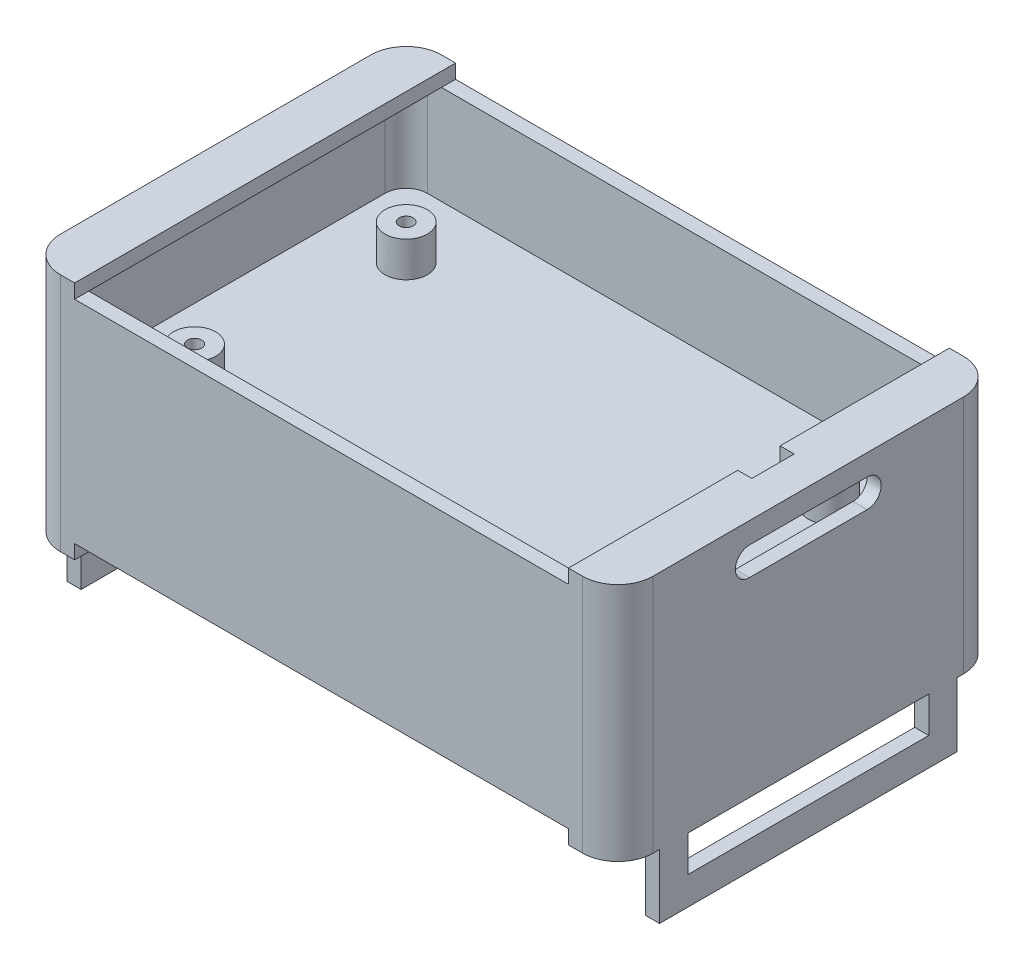
SolidWorks part; units mm, degrees
ref_plane "Front Plane" through (0, 0, 0) normal (0, 0, 1) x (1, 0, 0)
ref_plane "Top Plane" through (0, 0, 0) normal (0, 1, 0) x (1, 0, 0)
ref_plane "Right Plane" through (0, 0, 0) normal (1, 0, 0) x (0, 0, -1)
sketch "Sketch1" plane through (0, 0, 0) normal (0, 1, 0) x (1, 0, 0)
  line L1 (-37, -25) -> (37, -25)
  line L2 (-40, -22) -> (-40, 22)
  line L3 (-37, 25) -> (37, 25)
  line L4 (40, -22) -> (40, 22)
  line L5 (-40, -25) -> (40, 25) construction
  line L6 (-40, 25) -> (40, -25) construction
  arc A0 (-37, -25) -> (-40, -22) centre (-37, -22) cw
  arc A1 (37, -25) -> (40, -22) centre (37, -22) ccw
  arc A2 (37, 25) -> (40, 22) centre (37, 22) cw
  arc A3 (-40, 22) -> (-37, 25) centre (-37, 22) cw
  point P0 (0, 0)
  dimension "D3" = 3
  dimension "D1" = 80
  dimension "D2" = 50
extrude "Extrude-Thin1" add sketch "Sketch1" along normal blind 15 and the other way blind 15 thin thin type one direction wall 2
extrude "Boss-Extrude1" add sketch "Sketch1<2>" along normal blind 1
sketch "Sketch1<2>" plane through (0, 0, 0) normal (0, 1, 0) x (1, 0, 0) same geometry as "Sketch1"
sketch "Sketch3" plane through (0, 1, 0) normal (0, 1, 0) x (1, 0, 0)
  line L0 (-40, 0) -> (40, 0) construction
  line L1 (40, -22) -> (40, 22) construction
  line L2 (0, -25) -> (0, 25) construction
  line L3 (37, 25) -> (-37, 25) construction
  line L4 (-40, 22) -> (-40, -22) construction
  circle A0 centre (-30, 15) radius 1
  circle A1 centre (-30, 15) radius 3
  circle A2 centre (30, 15) radius 1
  circle A3 centre (30, 15) radius 3
  circle A4 centre (30, -15) radius 1
  circle A5 centre (30, -15) radius 3
  circle A6 centre (-30, -15) radius 1
  circle A7 centre (-30, -15) radius 3
  point P6 (0, 0)
  point P12 (0, 0)
  dimension "D3" = 2
  dimension "D1" = 10
  dimension "D2" = 10
  dimension "D4" = 2
extrude "Boss-Extrude2" add sketch "Sketch3" along normal blind 5
sketch "Sketch4" plane through (0, 15, 0) normal (0, 1, 0) x (1, 0, 0)
  line L22 (0, -27) -> (0, 27) construction
  line L23 (-35, 27) -> (-35, -27)
  line L24 (-40, 22) -> (-40, -22) construction
  line L25 (35, 27) -> (35, -27)
  line L26 (42, -22) -> (42, 22)
  line L27 (-37, -27) -> (37, -27)
  line L28 (-42, 22) -> (-42, -22)
  line L29 (37, 27) -> (-37, 27)
  line L30 (42, -22) -> (42, 22)
  line L31 (-37, -27) -> (37, -27)
  line L32 (-42, 22) -> (-42, -22)
  line L33 (37, 27) -> (-37, 27)
  line L34 (-40, 0) -> (40, 0) construction
  line L35 (40, -22) -> (40, 22) construction
  line L37 (33, -3) -> (37, -3)
  line L38 (33, -3) -> (33, 3)
  line L39 (33, 3) -> (37, 3)
  line L40 (37, -3) -> (37, 3)
  line L41 (33, -3) -> (37, 3) construction
  line L42 (33, 3) -> (37, -3) construction
  arc A23 (37, -27) -> (42, -22) centre (37, -22) ccw
  arc A24 (42, 22) -> (37, 27) centre (37, 22) ccw
  arc A25 (-42, -22) -> (-37, -27) centre (-37, -22) ccw
  arc A26 (-37, 27) -> (-42, 22) centre (-37, 22) ccw
  arc A27 (37, -27) -> (42, -22) centre (37, -22) ccw
  arc A28 (42, 22) -> (37, 27) centre (37, 22) ccw
  arc A29 (-42, -22) -> (-37, -27) centre (-37, -22) ccw
  arc A30 (-37, 27) -> (-42, 22) centre (-37, 22) ccw
  point P10 (0, 0)
  point P17 (35, 0)
  point P22 (0, 0)
  arc M11 (-42, -22) -> (-37, -27) centre (-37, -22) ccw
  line M12 (-37, -27) -> (37, -27)
  arc M13 (37, -27) -> (42, -22) centre (37, -22) ccw
  line M14 (42, -22) -> (42, 22)
  arc M15 (42, 22) -> (37, 27) centre (37, 22) ccw
  line M16 (37, 27) -> (-37, 27)
  arc M17 (-37, 27) -> (-42, 22) centre (-37, 22) ccw
  line M18 (-42, 22) -> (-42, -22)
  arc M19 (-37, -25) -> (-40, -22) centre (-37, -22) cw
  line M20 (-40, -22) -> (-40, 22)
  arc M21 (-40, 22) -> (-37, 25) centre (-37, 22) cw
  line M22 (-37, 25) -> (37, 25)
  arc M23 (37, 25) -> (40, 22) centre (37, 22) cw
  line M24 (40, 22) -> (40, -22)
  arc M25 (40, -22) -> (37, -25) centre (37, -22) cw
  line M26 (37, -25) -> (-37, -25)
  dimension "D2" = 5
  dimension "D3" = 6
  dimension "D4" = 4
  dimension "D1" = 0
extrude "Boss-Extrude3" add sketch "Sketch4" along normal blind 2 contours L23 M16 M17 M18 M11 M12 M26 M19 M20 M21 M22 | L23 M22 M21 M20 M19 M26 | L40 L37 L25 L39 M26 M25 M24 M23 M22 | L25 M16 M22 M23 M24 M25 M26 M12 M13 M14 M15 region at (-40.3792, 15, 0) region at (-37.4713, 15, 0) region at (40.3792, 15, 0) region at (37.5467, 15, 0)
extrude "Boss-Extrude4" add sketch "Sketch4<3>" against normal blind 2 from surface contours L23 M22 M21 M20 M19 M26 | L23 M16 M17 M18 M11 M12 M26 M19 M20 M21 M22 | L40 L37 L25 L39 M26 M25 M24 M23 M22 | L25 M16 M22 M23 M24 M25 M26 M12 M13 M14 M15 region at (-40.3792, 15, 0) region at (-37.4713, 15, 0) region at (40.3792, 15, 0) region at (37.5467, 15, 0) starting at face at (0, -15, 0)
sketch "Sketch4<3>" plane through (0, 15, 0) normal (0, 1, 0) x (1, 0, 0) same geometry as "Sketch4"
sketch "Sketch5" plane through (-42, 0, 0) normal (-1, 0, 0) x (0, 0, 1)
  line L0 (0, -17) -> (0, 17) construction
  line L1 (-22, 17) -> (22, 17) construction
  line L2 (-21.0836, -7.9043) -> (21.0836, -7.9043)
  line L3 (-17.0836, -22.0957) -> (17.0836, -22.0957)
  line L4 (-17.0836, -22.0957) -> (-17.0836, -11.9043)
  line L5 (-17.0836, -11.9043) -> (17.0836, -11.9043)
  line L6 (17.0836, -22.0957) -> (17.0836, -11.9043)
  line L7 (-17.0836, -22.0957) -> (17.0836, -11.9043) construction
  line L8 (-17.0836, -11.9043) -> (17.0836, -22.0957) construction
  line L9 (21.0836, -26.0957) -> (21.0836, -7.9043)
  line L10 (-21.0836, -26.0957) -> (21.0836, -26.0957)
  line L11 (-21.0836, -26.0957) -> (-21.0836, -7.9043)
  line L12 (-21.0836, -17) -> (21.0836, -17)
  point P6 (0, 0)
  line M12 (-22, -17) -> (22, -17)
  dimension "D1" = 4
extrude "Boss-Extrude5" add sketch "Sketch5" against normal blind 2 contours L11 L4 L5 L6 L9 L2 M12 | L11 L10 L9 L6 L3 L4 M12 | L6 L5 L4 M12 region at (-42, -10.7895, 0) region at (-42, -23.2105, 0) region at (-42, -14.4522, 0)
extrude "Boss-Extrude6" add sketch "Sketch5<3>" along normal blind 2 from surface contours L11 L4 L5 L6 L9 L2 M12 | L6 L5 L4 M12 | L11 L10 L9 L6 L3 L4 M12 region at (-42, -10.7895, 0) region at (-42, -23.2105, 0) region at (-42, -14.4522, 0) starting at face at (42, 0, 0)
sketch "Sketch5<3>" plane through (-42, 0, 0) normal (-1, 0, 0) x (0, 0, 1) same geometry as "Sketch5"
sketch "Sketch7" plane through (42, 0, 0) normal (1, 0, 0) x (0, 0, -1)
  line L0 (0, -17) -> (0, 17) construction
  line L1 (-22, 17) -> (22, 17) construction
  line L2 (-8.3383, 12) -> (8.3383, 12) construction
  line L3 (-8.3383, 14) -> (8.3383, 14)
  line L4 (-8.3383, 10) -> (8.3383, 10)
  arc A0 (-8.3383, 14) -> (-8.3383, 10) centre (-8.3383, 12) ccw
  arc A1 (8.3383, 10) -> (8.3383, 14) centre (8.3383, 12) ccw
  point P6 (0, 0)
  point P9 (0, 12)
  dimension "D1" = 5
  dimension "D2" = 4
extrude "Cut-Extrude1" cut sketch "Sketch7" against normal through all
